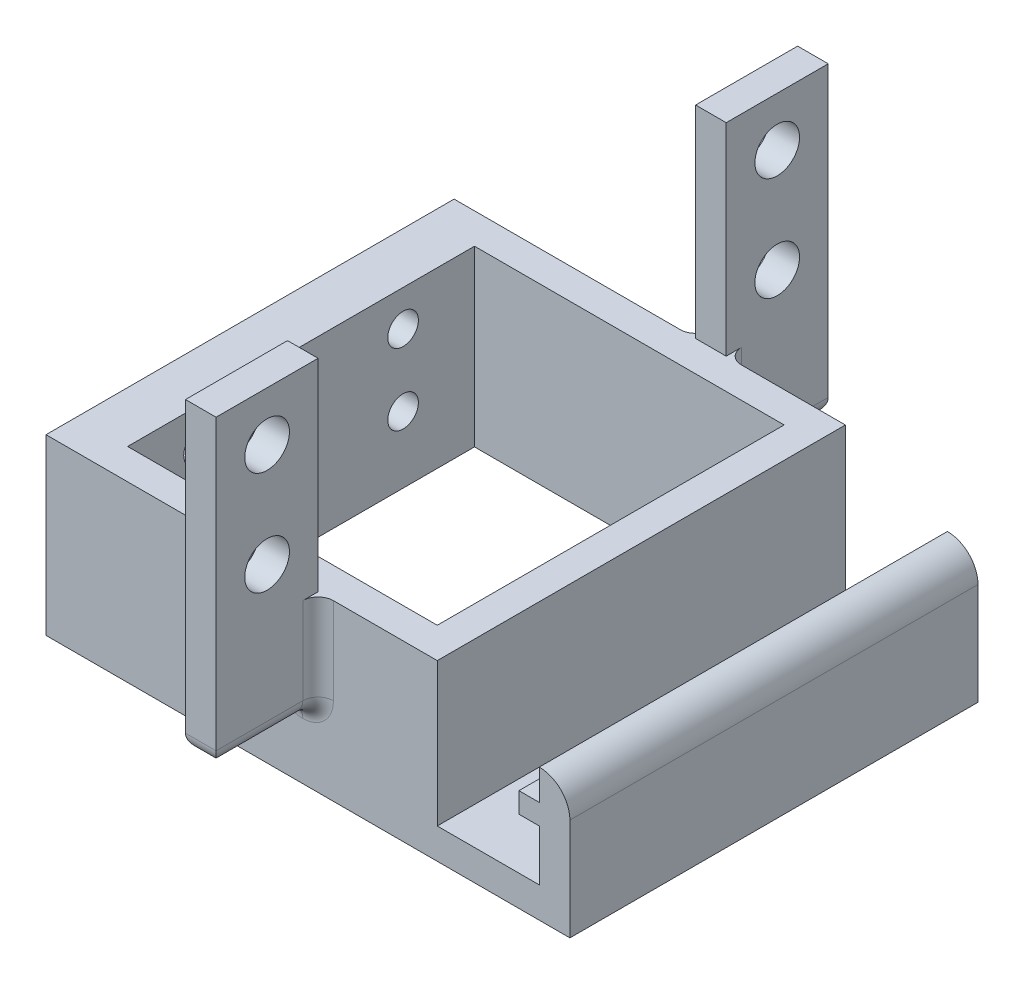
SolidWorks part; units mm, degrees
ref_plane "Front Plane" through (0, 0, 0) normal (0, 0, 1) x (1, 0, 0)
ref_plane "Top Plane" through (0, 0, 0) normal (0, 1, 0) x (1, 0, 0)
ref_plane "Right Plane" through (0, 0, 0) normal (1, 0, 0) x (0, 0, -1)
sketch "Sketch1" plane through (0, 0, 0) normal (1, 0, 0) x (0, 0, -1)
  line L1 (0, 0) -> (40, 0)
  line L2 (0, 0) -> (0, 3)
  line L3 (0, 3) -> (40, 3)
  line L4 (40, 0) -> (40, 3)
  dimension "D1" = 3
  dimension "D2" = 40
extrude "Boss-Extrude1" add sketch "Sketch1" along normal blind 51.35
sketch "Sketch2" plane through (0, 3, 0) normal (0, 1, 0) x (1, 0, 0)
  line L0 (51.35, 0) -> (0, 0) construction
  line L1 (51.35, 40) -> (48.35, 40)
  line L2 (51.35, 40) -> (51.35, 0)
  line L3 (51.35, 0) -> (48.35, 0)
  line L4 (48.35, 40) -> (48.35, 0)
  dimension "D1" = 3
extrude "Boss-Extrude2" add sketch "Sketch2" along normal blind 10
fillet "Fillet1" radius 3 1 edges at (51.35, 13, -20)
sketch "Sketch3" plane through (48.35, 0, 0) normal (-1, 0, 0) x (0, 0, 1)
  line L0 (0, 13) -> (0, 3) construction
  line L1 (0, 10) -> (-40, 10)
  line L2 (0, 10) -> (0, 8)
  line L3 (0, 8) -> (-40, 8)
  line L4 (-40, 10) -> (-40, 8)
  line L5 (-40, 13) -> (-40, 3) construction
  line L6 (-40, 3) -> (0, 3) construction
  dimension "D1" = 2
  dimension "D2" = 5
extrude "Boss-Extrude3" add sketch "Sketch3" along normal blind 2
sketch "Sketch4" plane through (0, 3, 0) normal (0, 1, 0) x (1, 0, 0)
  line L0 (48.35, 0) -> (0, 0) construction
  line L1 (0, 40) -> (3, 40)
  line L2 (0, 40) -> (0, 0)
  line L3 (0, 0) -> (3, 0)
  line L4 (5, 37) -> (5, 3)
  line L5 (46.35, 0) -> (46.35, 40) construction
  line L6 (3, 40) -> (38.35, 40)
  line L8 (5, 37) -> (35.35, 37)
  line L9 (38.35, 40) -> (38.35, 37)
  line L10 (3, 0) -> (38.35, 0)
  line L12 (5, 3) -> (35.35, 3)
  line L13 (38.35, 0) -> (38.35, 3)
  line L16 (38.35, 37) -> (38.35, 3)
  line L18 (35.35, 37) -> (35.35, 3)
  dimension "D1" = 3
  dimension "D2" = 3
  dimension "D3" = 3
  dimension "D4" = 8
  dimension "D5" = 3
extrude "Boss-Extrude4" add sketch "Sketch4" along normal blind 14.04
sketch "Sketch5" plane through (0, 0, 0) normal (0, 0, 1) x (1, 0, 0)
  line L0 (0, 17.04) -> (0, 0) construction
  line L1 (23.67, 7.04) -> (26.67, 7.04)
  line L2 (23.67, 7.04) -> (23.67, 36.86)
  line L3 (23.67, 36.86) -> (26.67, 36.86)
  line L4 (26.67, 7.04) -> (26.67, 36.86)
  line L5 (0, 17.04) -> (38.35, 17.04) construction
  dimension "D1" = 23.67
  dimension "D2" = 3
  dimension "D3" = 10
  dimension "D4" = 29.82
extrude "Boss-Extrude5" add sketch "Sketch5" along normal blind 10
ref_plane "Plane1" through (0, 0, -20) normal (0, 0, -1) x (-1, 0, 0)
mirror "Mirror2" about plane through (0, 0, -20) normal (0, 0, -1) of "Boss-Extrude5"
fillet "Fillet3" radius 1.5 10 edges at (23.67, 12.04, -40) (26.67, 12.04, 0) (23.67, 7.04, -45) (26.67, 7.04, -45) (25.17, 7.04, -50) (26.67, 12.04, -40) (23.67, 12.04, 0) (25.17, 7.04, 10) (26.67, 7.04, 5) (23.67, 7.04, 5)
sketch "Sketch6" plane through (26.67, 0, 0) normal (1, 0, 0) x (0, 0, -1)
  line L0 (-5, 32.035) -> (-5, 21.865) construction
  line L1 (0, 17.04) -> (-1.5, 17.04) construction
  line L2 (0, 17.04) -> (0, 36.86) construction
  circle A0 centre (-5, 32.035) radius 2.19
  circle A1 centre (-5, 21.865) radius 2.19
  point P4 (-5, 26.95)
  dimension "D1" = 4.38
  dimension "D2" = 4.38
  dimension "D3" = 10.17
  dimension "D4" = 9.91
  dimension "D5" = 5
extrude "Cut-Extrude1" cut sketch "Sketch6" against normal through all
mirror "Mirror3" about plane through (0, 0, -20) normal (0, 0, -1) of "Cut-Extrude1"
sketch "Sketch7" plane through (0, 0, 0) normal (-1, 0, 0) x (0, 0, 1)
  line L1 (-10, 13.52) -> (-10, 6.52) construction
  line L2 (-40, 17.04) -> (0, 17.04) construction
  line L4 (0, 17.04) -> (0, 0) construction
  circle A2 centre (-10, 13.52) radius 1.5
  circle A3 centre (-10, 6.52) radius 1.5
  point P0 (-10, 10.02)
  dimension "D1" = 7
  dimension "D2" = 7.02
  dimension "D3" = 3
  dimension "D4" = 3
  dimension "D5" = 10
extrude "Cut-Extrude2" cut sketch "Sketch7" against normal up to next
mirror "Mirror4" about plane through (0, 0, -20) normal (0, 0, -1) of "Cut-Extrude2"
sketch "Sketch8" plane through (0, 3, 0) normal (0, 1, 0) x (1, 0, 0)
  line L1 (5, 37) -> (35.35, 37)
  line L2 (5, 37) -> (5, 3)
  line L3 (5, 3) -> (35.35, 3)
  line L4 (35.35, 37) -> (35.35, 3)
extrude "Cut-Extrude3" cut sketch "Sketch8" against normal up to surface (3 mm away) up to face at (25.675, 0, -20)
equation "\"D4@Sketch5\"=10+19.82"
equation "\"D4@Sketch6\"=19.82/2"
